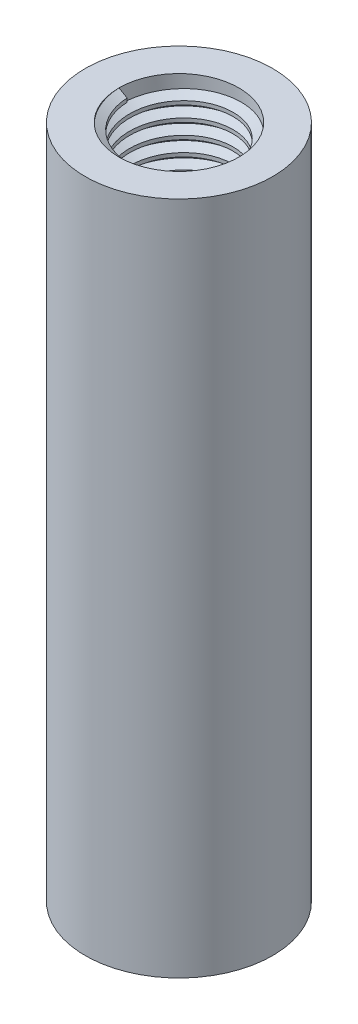
SolidWorks part; units mm, degrees
ref_plane "Front Plane" through (0, 0, 0) normal (0, 0, 1) x (1, 0, 0)
ref_plane "Top Plane" through (0, 0, 0) normal (0, 1, 0) x (1, 0, 0)
ref_plane "Right Plane" through (0, 0, 0) normal (1, 0, 0) x (0, 0, -1)
sketch "Sketch1" plane through (0, 0, 0) normal (0, 1, 0) x (1, 0, 0)
  circle A0 centre (0, 0) radius 12.5
  dimension "D1" = 25
extrude "Boss-Extrude1" add sketch "Sketch1" along normal blind 90
sketch "Sketch2" plane through (0, 90, 0) normal (0, 1, 0) x (1, 0, 0)
  circle A0 centre (0, 0) radius 8
  dimension "D1" = 16
extrude "Cut-Extrude1" cut sketch "Sketch2" against normal blind 50
thread "Thread1" start angle 0, offset 0, length 35, pitch 2, diameter 16
ref_plane "Plane1" through (-8, 90, 0) normal (0, 0, 1) x (-1, 0, 0)
sketch "Thread Profile1" plane through (-8, 90, 0) normal (0, 0, 1) x (-1, 0, 0)
  line L0 (0, 0) -> (0, 2) construction
  line L11 (0, 0) -> (0, 1.75)
  line L12 (0, 1.75) -> (-1.0825, 1.125)
  line L13 (-1.0825, 1.125) -> (-1.0825, 0.625)
  line L15 (-1.0825, 0.625) -> (0, 0)
  line L17 (-1.0825, 0.875) -> (0, 0.875) construction
  point P2 (0, 0)
  dimension "Pitch" = 2
  dimension "Profile_Angle" = 60
  dimension "Profile_Land" = 0.5
  dimension "Profile_Height" = 1.0825
sketch "Sketch11" plane through (0, 40, 0) normal (0, 1, 0) x (1, 0, 0)
  circle A0 centre (0, 0) radius 2.25
  dimension "D1" = 4.5
extrude "Cut-Extrude2" cut sketch "Sketch11" against normal blind 15
thread "Thread2" pitch 0.7 profile "Thread Profile2" start angle 0, offset 0, length 10, pitch 0.7, diameter 4.5
ref_plane "Plane2" through (-2.25, 40, 0) normal (0, 0, 1) x (-1, 0, 0)
sketch "Thread Profile2" plane through (-2.25, 40, 0) normal (0, 0, 1) x (-1, 0, 0)
  line L0 (0, 0) -> (0, 0.7) construction
  line L11 (0, 0) -> (0, 0.6125)
  line L12 (0, 0.6125) -> (-0.3789, 0.3937)
  line L13 (-0.3789, 0.3937) -> (-0.3789, 0.2187)
  line L15 (-0.3789, 0.2187) -> (0, 0)
  line L17 (-0.3789, 0.3062) -> (0, 0.3062) construction
  point P2 (0, 0)
  dimension "Pitch" = 0.7
  dimension "Profile_Angle" = 60
  dimension "Profile_Land" = 0.175
  dimension "Profile_Height" = 0.3789
